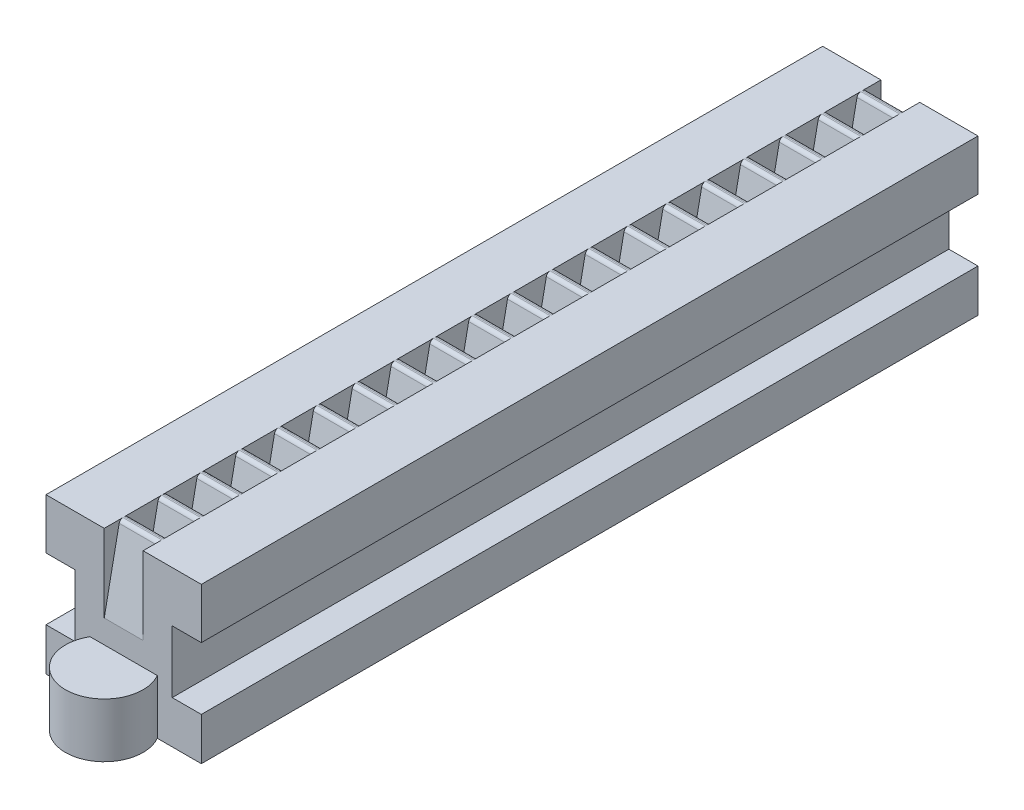
SolidWorks part; units mm, degrees
material "ABS"
ref_plane "Front Plane" through (0, 0, 0) normal (0, 0, 1) x (1, 0, 0)
ref_plane "Top Plane" through (0, 0, 0) normal (0, 1, 0) x (1, 0, 0)
ref_plane "Right Plane" through (0, 0, 0) normal (1, 0, 0) x (0, 0, -1)
sketch "Sketch2" plane through (0, 0, 0) normal (0, 0, 1) x (1, 0, 0)
  line L0 (0, 0) -> (10, 0)
  line L1 (10, 0) -> (10, 20)
  line L2 (10, 20) -> (2.5, 20)
  line L3 (2.5, 20) -> (2.5, 10)
  line L4 (2.5, 10) -> (0, 10)
  line L5 (0, 10) -> (0, 0)
  dimension "D1" = 10
  dimension "D2" = 20
  dimension "D3" = 10
  dimension "D4" = 7.5
extrude "Boss-Extrude1" add sketch "Sketch2" along normal blind 100 contours L5 L0 L1 L2 L3 L4
sketch "Sketch3" plane through (2.5, 0, 0) normal (-1, 0, 0) x (0, 0, 1)
  line L0 (0, 10) -> (1.9196, 19.5981)
  line L1 (2.4099, 20) -> (2.5901, 20)
  line L2 (3.0804, 19.5981) -> (5, 10)
  line L3 (100, 10) -> (0, 10) construction
  line L4 (0, 10) -> (5, 10)
  line L5 (100, 20) -> (0, 20) construction
  line L6 (5, 10) -> (6.9196, 19.5981)
  line L7 (8.0804, 19.5981) -> (10, 10)
  line L8 (5, 10) -> (10, 10)
  line L9 (7.4099, 20) -> (7.5901, 20)
  line L10 (10, 10) -> (11.9196, 19.5981)
  line L11 (13.0804, 19.5981) -> (15, 10)
  line L12 (10, 10) -> (15, 10)
  line L13 (12.4099, 20) -> (12.5901, 20)
  line L14 (15, 10) -> (16.9196, 19.5981)
  line L15 (18.0804, 19.5981) -> (20, 10)
  line L16 (15, 10) -> (20, 10)
  line L17 (17.4099, 20) -> (17.5901, 20)
  line L18 (20, 10) -> (21.9196, 19.5981)
  line L19 (23.0804, 19.5981) -> (25, 10)
  line L20 (20, 10) -> (25, 10)
  line L21 (22.4099, 20) -> (22.5901, 20)
  line L22 (25, 10) -> (26.9196, 19.5981)
  line L23 (28.0804, 19.5981) -> (30, 10)
  line L24 (25, 10) -> (30, 10)
  line L25 (27.4099, 20) -> (27.5901, 20)
  line L26 (30, 10) -> (31.9196, 19.5981)
  line L27 (33.0804, 19.5981) -> (35, 10)
  line L28 (30, 10) -> (35, 10)
  line L29 (32.4099, 20) -> (32.5901, 20)
  line L30 (35, 10) -> (36.9196, 19.5981)
  line L31 (38.0804, 19.5981) -> (40, 10)
  line L32 (35, 10) -> (40, 10)
  line L33 (37.4099, 20) -> (37.5901, 20)
  line L34 (40, 10) -> (41.9196, 19.5981)
  line L35 (43.0804, 19.5981) -> (45, 10)
  line L36 (40, 10) -> (45, 10)
  line L37 (42.4099, 20) -> (42.5901, 20)
  line L38 (45, 10) -> (46.9196, 19.5981)
  line L39 (48.0804, 19.5981) -> (50, 10)
  line L40 (45, 10) -> (50, 10)
  line L41 (47.4099, 20) -> (47.5901, 20)
  line L42 (50, 10) -> (51.9196, 19.5981)
  line L43 (53.0804, 19.5981) -> (55, 10)
  line L44 (50, 10) -> (55, 10)
  line L45 (52.4099, 20) -> (52.5901, 20)
  line L46 (55, 10) -> (56.9196, 19.5981)
  line L47 (58.0804, 19.5981) -> (60, 10)
  line L48 (55, 10) -> (60, 10)
  line L49 (57.4099, 20) -> (57.5901, 20)
  line L50 (60, 10) -> (61.9196, 19.5981)
  line L51 (63.0804, 19.5981) -> (65, 10)
  line L52 (60, 10) -> (65, 10)
  line L53 (62.4099, 20) -> (62.5901, 20)
  line L54 (65, 10) -> (66.9196, 19.5981)
  line L55 (68.0804, 19.5981) -> (70, 10)
  line L56 (65, 10) -> (70, 10)
  line L57 (67.4099, 20) -> (67.5901, 20)
  line L58 (70, 10) -> (71.9196, 19.5981)
  line L59 (73.0804, 19.5981) -> (75, 10)
  line L60 (70, 10) -> (75, 10)
  line L61 (72.4099, 20) -> (72.5901, 20)
  line L62 (75, 10) -> (76.9196, 19.5981)
  line L63 (78.0804, 19.5981) -> (80, 10)
  line L64 (75, 10) -> (80, 10)
  line L65 (77.4099, 20) -> (77.5901, 20)
  line L66 (80, 10) -> (81.9196, 19.5981)
  line L67 (83.0804, 19.5981) -> (85, 10)
  line L68 (80, 10) -> (85, 10)
  line L69 (82.4099, 20) -> (82.5901, 20)
  line L70 (85, 10) -> (86.9196, 19.5981)
  line L71 (88.0804, 19.5981) -> (90, 10)
  line L72 (85, 10) -> (90, 10)
  line L73 (87.4099, 20) -> (87.5901, 20)
  line L74 (90, 10) -> (91.9196, 19.5981)
  line L75 (93.0804, 19.5981) -> (95, 10)
  line L76 (90, 10) -> (95, 10)
  line L77 (92.4099, 20) -> (92.5901, 20)
  line L78 (95, 10) -> (96.9196, 19.5981)
  line L79 (98.0804, 19.5981) -> (100, 10)
  line L80 (95, 10) -> (100, 10)
  line L81 (97.4099, 20) -> (97.5901, 20)
  arc A0 (2.5901, 20) -> (3.0804, 19.5981) centre (2.5901, 19.5) cw
  arc A1 (1.9196, 19.5981) -> (2.4099, 20) centre (2.4099, 19.5) cw
  arc A2 (7.5901, 20) -> (8.0804, 19.5981) centre (7.5901, 19.5) cw
  arc A3 (6.9196, 19.5981) -> (7.4099, 20) centre (7.4099, 19.5) cw
  arc A4 (12.5901, 20) -> (13.0804, 19.5981) centre (12.5901, 19.5) cw
  arc A5 (11.9196, 19.5981) -> (12.4099, 20) centre (12.4099, 19.5) cw
  arc A6 (17.5901, 20) -> (18.0804, 19.5981) centre (17.5901, 19.5) cw
  arc A7 (16.9196, 19.5981) -> (17.4099, 20) centre (17.4099, 19.5) cw
  arc A8 (22.5901, 20) -> (23.0804, 19.5981) centre (22.5901, 19.5) cw
  arc A9 (21.9196, 19.5981) -> (22.4099, 20) centre (22.4099, 19.5) cw
  arc A10 (27.5901, 20) -> (28.0804, 19.5981) centre (27.5901, 19.5) cw
  arc A11 (26.9196, 19.5981) -> (27.4099, 20) centre (27.4099, 19.5) cw
  arc A12 (32.5901, 20) -> (33.0804, 19.5981) centre (32.5901, 19.5) cw
  arc A13 (31.9196, 19.5981) -> (32.4099, 20) centre (32.4099, 19.5) cw
  arc A14 (37.5901, 20) -> (38.0804, 19.5981) centre (37.5901, 19.5) cw
  arc A15 (36.9196, 19.5981) -> (37.4099, 20) centre (37.4099, 19.5) cw
  arc A16 (42.5901, 20) -> (43.0804, 19.5981) centre (42.5901, 19.5) cw
  arc A17 (41.9196, 19.5981) -> (42.4099, 20) centre (42.4099, 19.5) cw
  arc A18 (47.5901, 20) -> (48.0804, 19.5981) centre (47.5901, 19.5) cw
  arc A19 (46.9196, 19.5981) -> (47.4099, 20) centre (47.4099, 19.5) cw
  arc A20 (52.5901, 20) -> (53.0804, 19.5981) centre (52.5901, 19.5) cw
  arc A21 (51.9196, 19.5981) -> (52.4099, 20) centre (52.4099, 19.5) cw
  arc A22 (57.5901, 20) -> (58.0804, 19.5981) centre (57.5901, 19.5) cw
  arc A23 (56.9196, 19.5981) -> (57.4099, 20) centre (57.4099, 19.5) cw
  arc A24 (62.5901, 20) -> (63.0804, 19.5981) centre (62.5901, 19.5) cw
  arc A25 (61.9196, 19.5981) -> (62.4099, 20) centre (62.4099, 19.5) cw
  arc A26 (67.5901, 20) -> (68.0804, 19.5981) centre (67.5901, 19.5) cw
  arc A27 (66.9196, 19.5981) -> (67.4099, 20) centre (67.4099, 19.5) cw
  arc A28 (72.5901, 20) -> (73.0804, 19.5981) centre (72.5901, 19.5) cw
  arc A29 (71.9196, 19.5981) -> (72.4099, 20) centre (72.4099, 19.5) cw
  arc A30 (77.5901, 20) -> (78.0804, 19.5981) centre (77.5901, 19.5) cw
  arc A31 (76.9196, 19.5981) -> (77.4099, 20) centre (77.4099, 19.5) cw
  arc A32 (82.5901, 20) -> (83.0804, 19.5981) centre (82.5901, 19.5) cw
  arc A33 (81.9196, 19.5981) -> (82.4099, 20) centre (82.4099, 19.5) cw
  arc A34 (87.5901, 20) -> (88.0804, 19.5981) centre (87.5901, 19.5) cw
  arc A35 (86.9196, 19.5981) -> (87.4099, 20) centre (87.4099, 19.5) cw
  arc A36 (92.5901, 20) -> (93.0804, 19.5981) centre (92.5901, 19.5) cw
  arc A37 (91.9196, 19.5981) -> (92.4099, 20) centre (92.4099, 19.5) cw
  arc A38 (97.5901, 20) -> (98.0804, 19.5981) centre (97.5901, 19.5) cw
  arc A39 (96.9196, 19.5981) -> (97.4099, 20) centre (97.4099, 19.5) cw
  point P11 (3, 20)
  point P14 (2, 20)
  line M4 (0, 10) -> (100, 10)
  line M6 (100, 20) -> (0, 20)
  dimension "D4" = 0.5
  dimension "D1" = 5
  dimension "D2" = 1
  dimension "D3" = 2
  dimension "D5" = 20
extrude "Boss-Extrude2" add sketch "Sketch3" along normal up to surface (2.5 mm away) contours A1 L0 L2 A0 M4 M6 | A3 L6 L7 A2 M4 M6 | A5 L10 L11 A4 M4 M6 | A7 L14 L15 A6 M4 M6 | A9 L18 L19 A8 M4 M6 | A11 L22 L23 A10 M4 M6 | A13 L26 L27 A12 M4 M6 | A15 L30 L31 A14 M4 M6 | A17 L34 L35 A16 M4 M6 | A19 L38 L39 A18 M4 M6 | A21 L42 L43 A20 M4 M6 | A23 L46 L47 A22 M4 M6 | A25 L50 L51 A24 M4 M6 | A27 L54 L55 A26 M4 M6 | A29 L58 L59 A28 M4 M6 | A31 L62 L63 A30 M4 M6 | A33 L66 L67 A32 M4 M6 | A35 L70 L71 A34 M4 M6 | A39 L78 L79 A38 M4 M6 | L74 A37 L77 A36 L75 L76 region at (2.5, 13.8755, 2.5) region at (2.5, 13.8755, 7.5) region at (2.5, 13.8755, 12.5) region at (2.5, 13.8755, 17.5) region at (2.5, 13.8755, 22.5) region at (2.5, 13.8755, 27.5) region at (2.5, 13.8755, 32.5) region at (2.5, 13.8755, 37.5) region at (2.5, 13.8755, 42.5) region at (2.5, 13.8755, 47.5) region at (2.5, 13.8755, 52.5) region at (2.5, 13.8755, 57.5) region at (2.5, 13.8755, 62.5) region at (2.5, 13.8755, 67.5) region at (2.5, 13.8755, 72.5) region at (2.5, 13.8755, 77.5) region at (2.5, 13.8755, 82.5) region at (2.5, 13.8755, 87.5) region at (2.5, 13.8755, 97.5) up to face at (0, 5, 50)
mirror "Mirror1" about plane through (0, 10, 100) normal (1, 0, 0) of "Boss-Extrude2", "Boss-Extrude1"
sketch "Sketch4" plane through (0, 0, 0) normal (0, -1, 0) x (1, 0, 0)
  line L0 (-10, 100) -> (10, 100) construction
  line L1 (-10, 0) -> (10, 0) construction
  circle A0 centre (0, 102.5) radius 5
  circle A1 centre (0, 2.5) radius 5.125
  dimension "D1" = 10
  dimension "D2" = 2.5
  dimension "D3" = 10.25
  dimension "D4" = 2.5
extrude "Boss-Extrude3" add sketch "Sketch4" against normal blind 7 contours A0
extrude "Cut-Extrude1" cut sketch "Sketch4<3>" against normal blind 7 contours A1
sketch "Sketch4<3>" plane through (0, 0, 0) normal (0, -1, 0) x (1, 0, 0) same geometry as "Sketch4"
sketch "Sketch7" plane through (0, 0, 0) normal (0, 0, -1) x (-1, 0, 0)
  line L0 (10, 0) -> (10, 20) construction
  line L1 (10, 13.5) -> (6.25, 13.5)
  line L2 (10, 13.5) -> (10, 5.5)
  line L3 (10, 5.5) -> (6.25, 5.5)
  line L4 (6.25, 13.5) -> (6.25, 5.5)
  line L5 (10, 20) -> (2.5, 20) construction
  line L6 (-10, 0) -> (-10, 20) construction
  line L7 (-6.25, 13.5) -> (-10, 13.5)
  line L8 (-6.25, 13.5) -> (-6.25, 5.5)
  line L9 (-6.25, 5.5) -> (-10, 5.5)
  line L10 (-10, 13.5) -> (-10, 5.5)
  line M13 (-10, 20) -> (-10, 0)
  dimension "D1" = 8
  dimension "D2" = 6.5
  dimension "D3" = 3.75
  dimension "D4" = 3.75
extrude "Cut-Extrude4" cut sketch "Sketch7" against normal blind 145 contours L9 L8 L7 M13 | L1 L4 L3 L2 region at (8.125, 9.5, 0)
